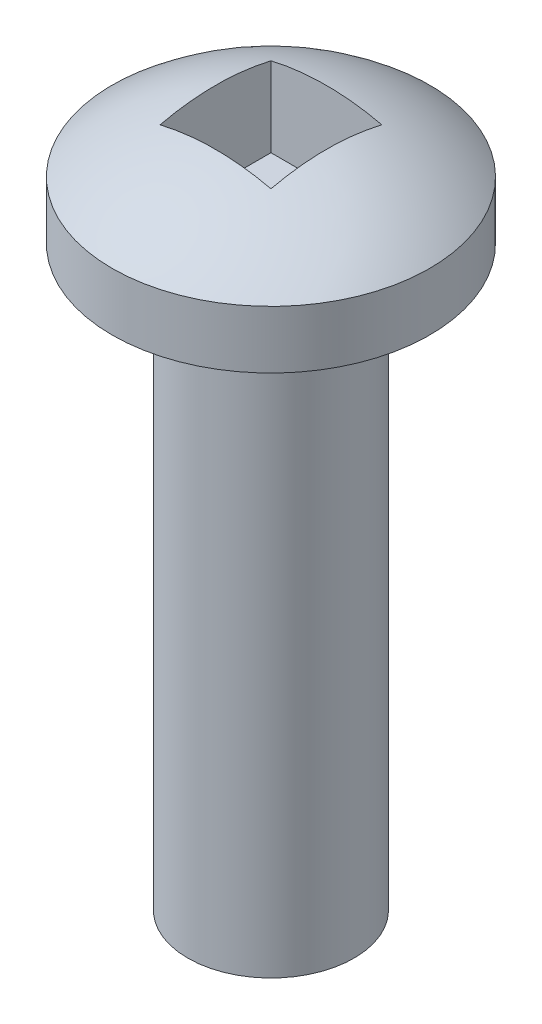
SolidWorks part; units mm, degrees
material "Cast Alloy Steel"
ref_plane "Front Plane" through (0, 0, 0) normal (0, 0, 1) x (1, 0, 0)
ref_plane "Top Plane" through (0, 0, 0) normal (0, 1, 0) x (1, 0, 0)
ref_plane "Right Plane" through (0, 0, 0) normal (1, 0, 0) x (0, 0, -1)
sketch "Sketch1" plane through (0, 0, 0) normal (0, 1, 0) x (1, 0, 0)
  circle A0 centre (0, 0) radius 1.8288
  dimension "D1" = 3.6576
extrude "Boss-Extrude1" add sketch "Sketch1" against normal blind 12.7
sketch "Sketch2" plane through (0, 0, 0) normal (0, 1, 0) x (1, 0, 0)
  circle A0 centre (0, 0) radius 3.4925
  dimension "D1" = 6.985
extrude "Boss-Extrude2" add sketch "Sketch2" along normal blind 1.27
dome "Dome1" faces to dome 1 distance 1.27 reverse direction no elliptical dome no face at (0, 1.27, 3.4925) parameters "D1"=1.27
ref_plane "Plane1" through (0, 2.54, 0) normal (0, 1, 0) x (1, 0, 0)
sketch "Sketch3" plane through (0, 2.54, 0) normal (0, 1, 0) x (1, 0, 0)
  line L1 (-1.2192, -1.2192) -> (1.2192, -1.2192)
  line L2 (-1.2192, -1.2192) -> (-1.2192, 1.2192)
  line L3 (-1.2192, 1.2192) -> (1.2192, 1.2192)
  line L4 (1.2192, -1.2192) -> (1.2192, 1.2192)
  line L5 (-1.2192, -1.2192) -> (1.2192, 1.2192) construction
  line L6 (-1.2192, 1.2192) -> (1.2192, -1.2192) construction
  point P0 (0, 0)
  dimension "D1" = 2.4384
extrude "Cut-Extrude1" cut sketch "Sketch3" against normal blind 2.032
